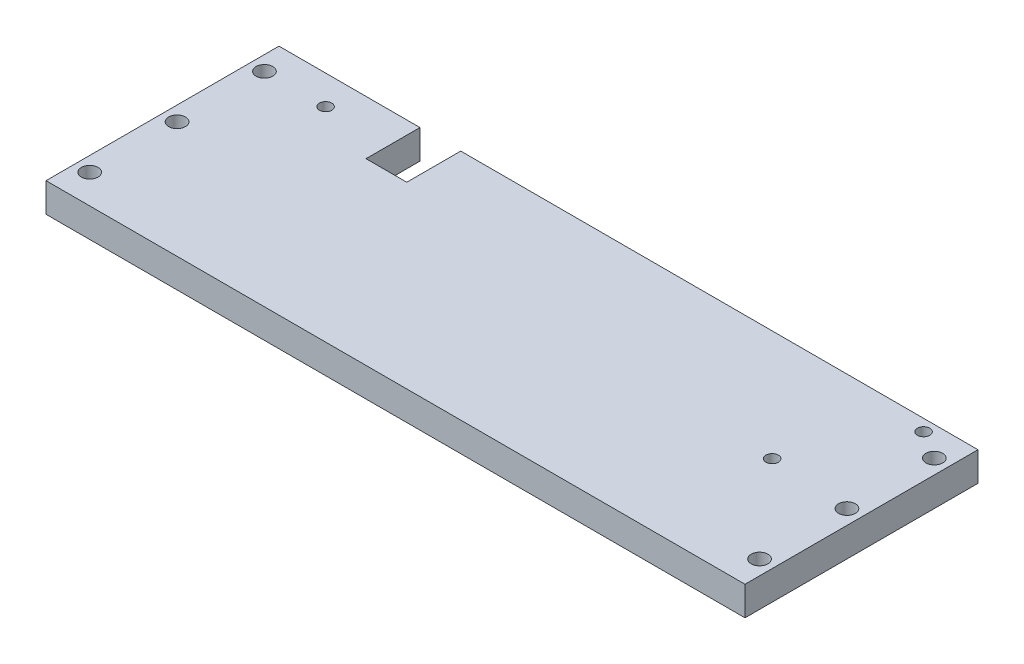
SolidWorks part; units mm, degrees
ref_plane "Front Plane" through (0, 0, 0) normal (0, 0, 1) x (1, 0, 0)
ref_plane "Top Plane" through (0, 0, 0) normal (0, 1, 0) x (1, 0, 0)
ref_plane "Right Plane" through (0, 0, 0) normal (1, 0, 0) x (0, 0, -1)
sketch "Sketch1" plane through (0, 0, 0) normal (0, 1, 0) x (1, 0, 0)
  line L1 (0, 0) -> (-152.4, 0)
  line L2 (0, 0) -> (0, 50.8)
  line L3 (0, 50.8) -> (-152.4, 50.8)
  line L4 (-152.4, 0) -> (-152.4, 50.8)
  dimension "D1" = 50.8
  dimension "D2" = 152.4
extrude "Boss-Extrude1" add sketch "Sketch1" along normal blind 6.35
sketch "Sketch2" plane through (0, 6.35, 0) normal (0, 1, 0) x (1, 0, 0)
  line L0 (0, 50.8) -> (-152.4, 50.8) construction
  line L1 (0, 0) -> (0, 50.8) construction
  line L2 (-152.4, 50.8) -> (-152.4, 0) construction
  circle A0 centre (-149.225, 44.45) radius 1.8288
  circle A1 centre (-149.225, 25.4) radius 1.8288
  circle A2 centre (-149.225, 6.35) radius 1.8288
  circle A3 centre (-3.175, 25.4) radius 1.8288
  circle A4 centre (-3.175, 44.45) radius 1.8288
  circle A5 centre (-3.175, 6.35) radius 1.8288
  dimension "D10" = 3.6576
  dimension "D11" = 3.6576
  dimension "D12" = 3.6576
  dimension "D13" = 3.6576
  dimension "D14" = 3.6576
  dimension "D15" = 3.6576
  dimension "D16" = 3.175
  dimension "D17" = 3.175
  dimension "D18" = 3.175
  dimension "D1" = 6.35
  dimension "D2" = 25.4
  dimension "D3" = 44.45
  dimension "D4" = 6.35
  dimension "D5" = 25.4
  dimension "D6" = 44.45
  dimension "D7" = 3.175
  dimension "D8" = 3.175
  dimension "D9" = 3.175
extrude "Cut-Extrude1" cut sketch "Sketch2" against normal blind 6.35
sketch "Sketch5" plane through (0, 6.35, 0) normal (0, 1, 0) x (1, 0, 0)
  line L0 (-121.666, 50.8) -> (-121.666, 39.035)
  line L1 (0, 50.8) -> (-152.4, 50.8) construction
  line L2 (-121.666, 39.035) -> (-112.776, 39.035)
  line L3 (-112.776, 39.035) -> (-112.776, 50.8)
  line L5 (-152.4, 50.8) -> (-152.4, 0) construction
  line L6 (-121.666, 50.8) -> (-112.776, 50.8)
  dimension "D1" = 39.624
  dimension "D2" = 8.89
extrude "Cut-Extrude2" cut sketch "Sketch5" against normal through all
sketch "Sketch6" plane through (0, 6.35, 0) normal (0, 1, 0) x (1, 0, 0)
  line L0 (-152.4, 50.8) -> (-152.4, 0) construction
  line L1 (-121.666, 50.8) -> (-152.4, 50.8) construction
  circle A0 centre (-135.89, 44.45) radius 1.8288
  dimension "D2" = 6.35
  dimension "D3" = 3.6576
  dimension "D1" = 16.51
hole_wizard "#6-32 Tapped Hole1" positions "Sketch11" profile "Sketch12" tap size "#6-32" standard "ANSI Inch" end condition up to next
sketch "Sketch11" plane through (0, 6.35, 0) normal (0, 1, 0) x (1, 0, 0)
  point P0 (-135.89, 44.45)
sketch "Sketch12" plane through (-135.89, 6.35, -44.45) normal (1, 0, 0) x (0, 0, 1)
  line L0 (0, 0) -> (0, 6.35)
  line L1 (0, 6.35) -> (1.3525, 6.35)
  line L2 (1.3525, 6.35) -> (1.3525, 0)
  line L5 (1.3525, 0) -> (0, 0)
  line L11 (0, -6.35) -> (0, 107.95) construction
  dimension "Thru Tap Drill Dia." = 2.7051
  dimension "Thru Tap Drill Depth" = 6.35
cosmetic thread "Hole Thread1" parameters "D2"=3.5052
sketch "Sketch13" plane through (0, 6.35, 0) normal (0, 1, 0) x (1, 0, 0)
  line L0 (0, 0) -> (0, 50.8) construction
  line L1 (0, 50.8) -> (-112.776, 50.8) construction
  circle A0 centre (-20.7518, 26.67) radius 1.8288
  circle A1 centre (-9.3218, 48.26) radius 1.8288
  dimension "D1" = 9.3218
  dimension "D2" = 20.7518
  dimension "D3" = 3.6576
  dimension "D4" = 3.6576
  dimension "D5" = 21.59
  dimension "D6" = 2.54
hole_wizard "#6-32 Tapped Hole2" positions "Sketch14" profile "Sketch15" tap size "#6-32" standard "ANSI Inch" end condition up to next
sketch "Sketch14" plane through (0, 6.35, 0) normal (0, 1, 0) x (1, 0, 0)
  point P0 (-9.3218, 48.26)
  point P3 (-20.7518, 26.67)
sketch "Sketch15" plane through (-9.3218, 6.35, -48.26) normal (1, 0, 0) x (0, 0, 1)
  line L0 (0, 0) -> (0, 6.35)
  line L1 (0, 6.35) -> (1.3525, 6.35)
  line L2 (1.3525, 6.35) -> (1.3525, 0)
  line L5 (1.3525, 0) -> (0, 0)
  line L11 (0, -6.35) -> (0, 107.95) construction
  dimension "Thru Tap Drill Dia." = 2.7051
  dimension "Thru Tap Drill Depth" = 6.35
cosmetic thread "Hole Thread2" parameters "D2"=3.5052
cosmetic thread "Hole Thread3" parameters "D2"=3.5052
